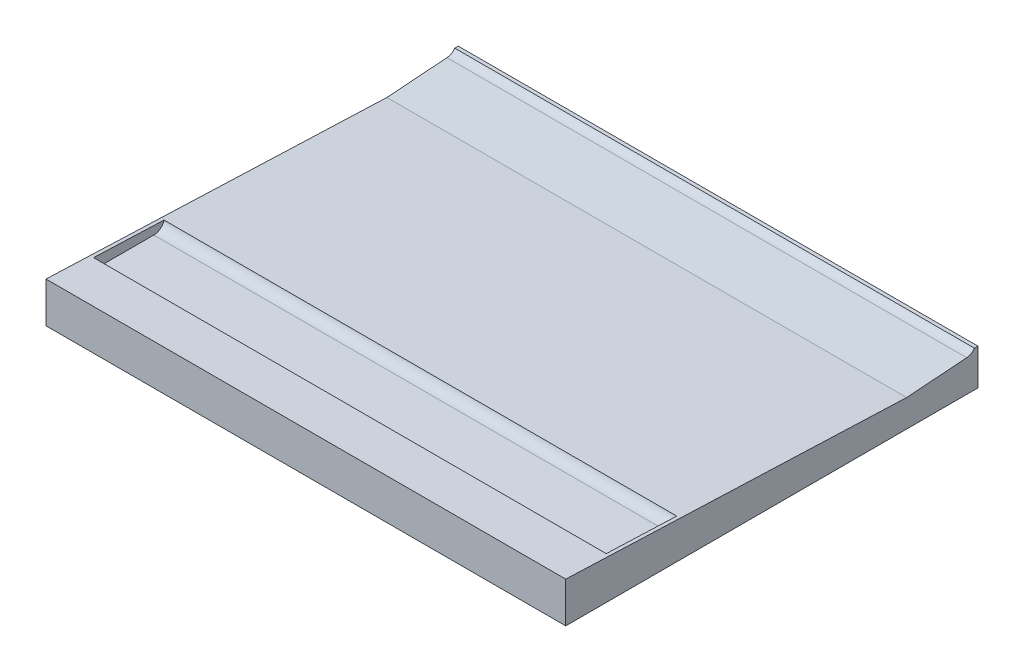
SolidWorks part; units mm, degrees
material "ABS"
ref_plane "Front Plane" through (0, 0, 0) normal (0, 0, 1) x (1, 0, 0)
ref_plane "Top Plane" through (0, 0, 0) normal (0, 1, 0) x (1, 0, 0)
ref_plane "Right Plane" through (0, 0, 0) normal (1, 0, 0) x (0, 0, -1)
sketch "Sketch1" plane through (0, 0, 0) normal (0, 1, 0) x (1, 0, 0)
  line L0 (-147.5, 0) -> (0, 0) construction
  line L1 (-147.5, 117) -> (147.5, 117)
  line L2 (-147.5, 117) -> (-147.5, -117)
  line L3 (-147.5, -117) -> (147.5, -117)
  line L4 (147.5, 117) -> (147.5, -117)
  line L5 (0, 0) -> (0, 117) construction
  dimension "D1" = 234
  dimension "D2" = 295
extrude "Boss-Extrude1" add sketch "Sketch1" along normal blind 28
sketch "Sketch2" plane through (-147.5, 0, 0) normal (-1, 0, 0) x (0, 0, 1)
  line L0 (117, 28) -> (-76.5, 20.5)
  line L1 (-117, 0) -> (117, 0) construction
  line L2 (-76.5, 20.5) -> (-117, 23.5)
  line L4 (-117, 28) -> (-117, 0) construction
  line L5 (-117, 23.5) -> (-117, 28)
  line L6 (-117, 28) -> (117, 28)
  dimension "D1" = 20.5
  dimension "D2" = 23.5
  dimension "D3" = 40.5
extrude "Cut-Extrude1" cut sketch "Sketch2" against normal blind 300
chamfer "Chamfer1" distance 5 angle 45 2 edges at (147.5, 0, 0) (-147.5, 0, 0)
chamfer "Chamfer2" distance 5 angle 45 1 edges at (0, 0, 117)
sketch "Sketch3" plane through (-147.5, 0, 0) normal (-1, 0, 0) x (0, 0, 1)
  line L1 (92, 33.2879) -> (52, 33.2879)
  line L2 (92, 33.2879) -> (92, 21.031)
  line L3 (92, 21.031) -> (52, 21.031)
  line L4 (52, 33.2879) -> (52, 21.031)
  line L5 (92, 27.031) -> (52, 25.4806) construction
  line L6 (-76.5, 20.5) -> (117, 28) construction
  line L7 (117, 28) -> (117, 5) construction
  dimension "D1" = 40
  dimension "D2" = 6
  dimension "D3" = 25
extrude "Cut-Extrude2" cut sketch "Sketch3" against normal blind 300
sketch "Sketch4" plane through (-147.5, 0, 0) normal (-1, 0, 0) x (0, 0, 1)
  line L0 (92, 27.031) -> (52, 25.4806)
  line L1 (52, 25.4806) -> (52, 21.031)
  line L2 (52, 21.031) -> (92, 21.031)
  line L3 (92, 21.031) -> (92, 27.031)
extrude "Boss-Extrude2" add sketch "Sketch4" against normal blind 2
mirror "Mirror1" about plane through (0, 0, 0) normal (1, 0, 0) of "Boss-Extrude2"
sketch "Sketch5" plane through (-147.5, 0, 0) normal (-1, 0, 0) x (0, 0, 1)
  line L4 (-117, 23.5) -> (-76.5, 20.5) construction
  line L5 (-117, 23.5) -> (-115, 23.3519)
  line L6 (-117, 23.5) -> (-117, 25.5)
  line L7 (-117, 25.5) -> (-115, 25.5)
  line L8 (-115, 23.3519) -> (-115, 25.5)
  dimension "D2" = 2
  dimension "D1" = 2
extrude "Boss-Extrude3" add sketch "Sketch5" against normal blind 295
fillet "Fillet1" radius 6 1 edges at (0, 23.3519, -115)
fillet "Fillet2" radius 6 2 edges at (0, 21.031, 92) (0, 21.031, 52)
chamfer "Chamfer3" distance 5 angle 45 1 edges at (0, 0, -117)
